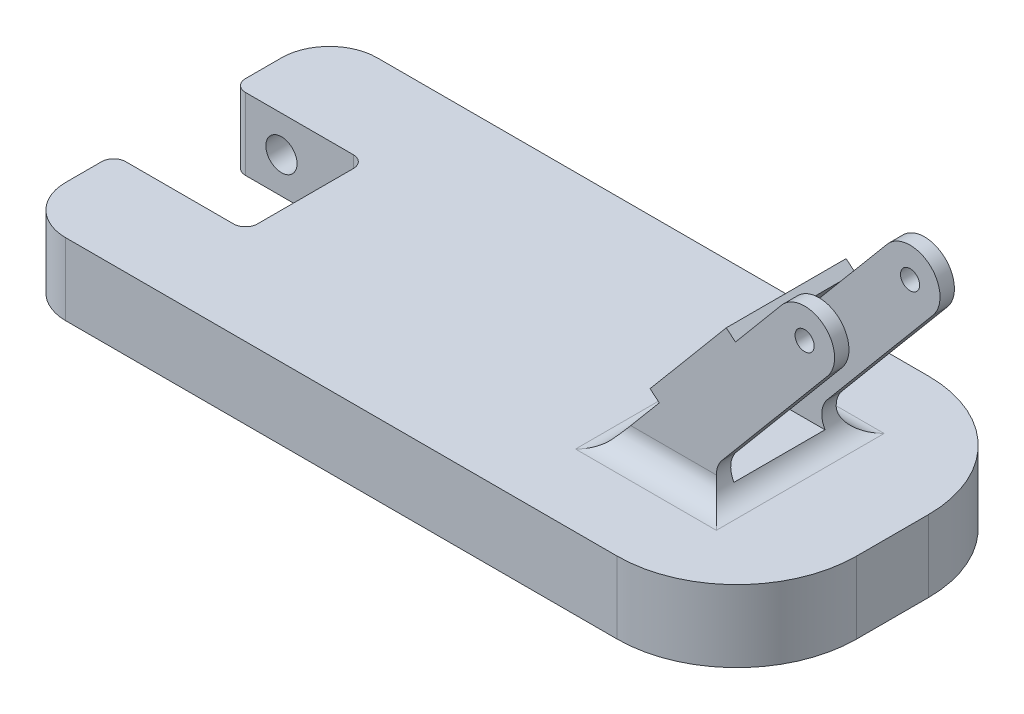
SolidWorks part; units mm, degrees
ref_plane "Front Plane" through (0, 0, 0) normal (0, 0, 1) x (1, 0, 0)
ref_plane "Top Plane" through (0, 0, 0) normal (0, 1, 0) x (1, 0, 0)
ref_plane "Right Plane" through (0, 0, 0) normal (1, 0, 0) x (0, 0, -1)
sketch "Sketch1" plane through (0, 0, 0) normal (0, 1, 0) x (1, 0, 0)
  line L0 (-150, 25) -> (-95, 25)
  line L1 (-150, 65) -> (150, 65)
  line L2 (-150, 65) -> (-150, 25)
  line L3 (-150, -65) -> (150, -65)
  line L4 (150, 65) -> (150, -65)
  line L5 (-150, 65) -> (150, -65) construction
  line L6 (-150, -65) -> (150, 65) construction
  line L7 (-95, 25) -> (-95, -25)
  line L8 (-95, -25) -> (-150, -25)
  line L9 (-150, -25) -> (-150, -65)
  point P0 (0, 0)
  dimension "D1" = 300
  dimension "D2" = 130
  dimension "D3" = 50
  dimension "D4" = 40
  dimension "D5" = 55
extrude "Boss-Extrude1" add sketch "Sketch1" along normal blind 30
sketch "Sketch2" plane through (0, 0, 65) normal (0, 0, 1) x (1, 0, 0)
  line L0 (90, 30) -> (147.8509, 98.944)
  line L1 (-150, 30) -> (150, 30) construction
  line L2 (150, 30) -> (150, 0) construction
  line L3 (70.8489, 46.0697) -> (128.6998, 115.0137)
  line L4 (70.8489, 46.0697) -> (57.3648, 30)
  line L5 (57.3648, 30) -> (90, 30)
  line L6 (128.6998, 115.0137) -> (147.8509, 98.944) construction
  arc A0 (147.8509, 98.944) -> (128.6998, 115.0137) centre (138.2753, 106.9788) ccw
  circle A1 centre (138.2753, 106.9788) radius 4
  dimension "D5" = 8
  dimension "D1" = 50
  dimension "D2" = 60
  dimension "D3" = 90
  dimension "D4" = 25
extrude "Boss-Extrude2" add sketch "Sketch2" against normal blind 50 from offset 40 offset against normal yes
sketch "Sketch4" plane through (0, 0, 0) normal (1, 0, 0) x (0, 0, -1)
  line L0 (25, 30) -> (-25, 30) construction
  line L1 (-19, 35) -> (19, 35)
  line L2 (-19, 35) -> (-19, 124.6927)
  line L3 (-19, 124.6927) -> (19, 124.6927)
  line L4 (19, 35) -> (19, 124.6927)
  line L5 (-19, 35) -> (19, 124.6927) construction
  line L6 (-19, 124.6927) -> (19, 35) construction
  line L7 (25, 98.944) -> (25, 119.4788) construction
  line L8 (-25, 30) -> (-25, 98.944) construction
  point P0 (0, 79.8464)
  dimension "D1" = 5
  dimension "D2" = 6
  dimension "D3" = 6
extrude "Cut-Extrude1" cut sketch "Sketch4" along normal through all
sketch "Sketch5" plane through (0, 0, -25) normal (0, 0, 1) x (1, 0, 0)
  line L4 (-150, 0) -> (-95, 0)
  line L5 (-95, 0) -> (-95, 30)
  line L6 (-95, 30) -> (-150, 30)
  line L7 (-150, 30) -> (-150, 0)
  line L8 (-150, 0) -> (-95, 0)
  line L9 (-95, 0) -> (-95, 30)
  line L10 (-95, 30) -> (-150, 30) construction
  line L11 (-150, 30) -> (-150, 0)
  circle A0 centre (-130, 15) radius 6.5
  dimension "D2" = 13
  dimension "D3" = 15
  dimension "D4" = 35
  dimension "D1" = 0
extrude "Cut-Extrude3" cut sketch "Sketch5" against normal blind 10 and the other way blind 60 contours A0 region at (-130, 15, -25)
fillet "Fillet1" radius 50 2 edges at (150, 15, -65) (150, 15, 65)
fillet "Fillet2" radius 10 4 edges at (57.3648, 30, 0) (73.6824, 30, -25) (90, 30, 0) (73.6824, 30, 25)
fillet "Fillet3" radius 20 2 edges at (-150, 15, -65) (-150, 15, 65)
fillet "Fillet4" radius 5 4 edges at (-95, 15, -25) (-95, 15, 25) (-150, 15, 25) (-150, 15, -25)
sketch "Sketch6" plane through (18.8909, -15.8514, 0) normal (-0.766, 0.6428, 0) x (0.6428, 0.766, 0)
  line L0 (170.8322, 19) -> (170.8322, -19)
  line L1 (91.3818, 19) -> (91.3818, -19)
  line L2 (91.3818, 19) -> (91.3818, 25)
  line L3 (91.3818, -19) -> (91.3818, -25)
  line L4 (140.8322, 25) -> (140.8322, -25)
  line L8 (170.8322, 25) -> (72.9088, 25)
  line L9 (64.5178, 27.3396) -> (64.5178, -27.3396)
  line L10 (72.9088, -25) -> (170.8322, -25)
  line L11 (170.8322, -25) -> (170.8322, -19)
  line L12 (170.8322, -19) -> (66.3818, -19)
  line L13 (66.3818, -19) -> (66.3818, 19)
  line L14 (66.3818, 19) -> (170.8322, 19)
  line L15 (170.8322, 19) -> (170.8322, 25)
  line L16 (170.8322, 25) -> (72.5193, 25)
  line L17 (64.5178, 27.3396) -> (64.5178, -27.3396)
  line L18 (72.9088, -25) -> (170.8322, -25)
  line L19 (170.8322, -25) -> (170.8322, -19)
  line L21 (66.3818, -19) -> (66.3818, 19)
  line L23 (170.8322, 19) -> (170.8322, 25)
  ellipse E2 centre (72.9088, 35) end of major axis (85.9629, 35) minor radius 10 (64.5178, 27.3396) -> (72.9088, 25) ccw
  ellipse E3 centre (72.9088, -35) end of major axis (59.8547, -35) minor radius 10 (72.9088, -25) -> (64.5178, -27.3396) ccw
  ellipse E4 centre (72.9088, 35) end of major axis (85.9629, 35) minor radius 10 (64.5178, 27.3396) -> (72.9088, 25) ccw
  ellipse E5 centre (72.9088, -35) end of major axis (59.8547, -35) minor radius 10 (72.9088, -25) -> (64.5178, -27.3396) ccw
  line M12 (170.8322, 25) -> (72.9088, 25)
  line M16 (72.9088, -25) -> (170.8322, -25)
  line M17 (170.8322, -25) -> (170.8322, -19)
  line M18 (170.8322, -19) -> (66.3818, -19)
  line M20 (66.3818, 19) -> (170.8322, 19)
  line M21 (170.8322, 19) -> (170.8322, 25)
  dimension "D2" = 25
  dimension "D3" = 30
  dimension "D1" = 0
extrude "Boss-Extrude3" add sketch "Sketch6" along normal blind 5 contours L1 L0 M20 M18 | L3 M18 M16 M17 | L2 M20 M21 M12 region at (93.5231, 73.0917, -22) region at (93.5231, 73.0917, 0) region at (93.5231, 73.0917, 22)
